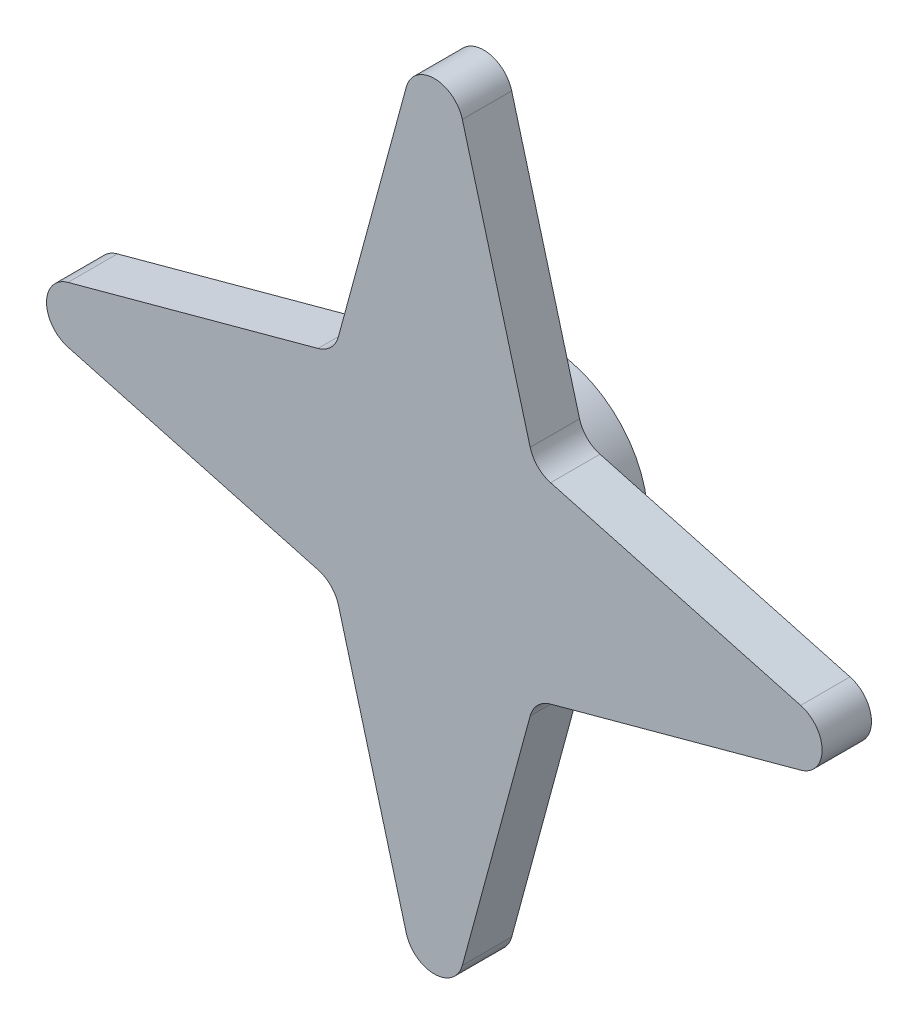
SolidWorks part; units mm, degrees
ref_plane "Front Plane" through (0, 0, 0) normal (0, 0, 1) x (1, 0, 0)
ref_plane "Top Plane" through (0, 0, 0) normal (0, 1, 0) x (1, 0, 0)
ref_plane "Right Plane" through (0, 0, 0) normal (1, 0, 0) x (0, 0, -1)
sketch "Sketch1" plane through (0, 0, 0) normal (0, 0, 1) x (1, 0, 0)
  line L0 (-1.7, 0) -> (-18.5, 0) construction
  line L1 (-8.6, 3.45) -> (-7.5895, 2.4395)
  line L2 (-8.6, -3.45) -> (-7.5895, -2.4395)
  line L5 (-8.6, 3.45) -> (-17.7618, 0.9651)
  line L6 (-8.6, -3.45) -> (-17.7618, -0.9651)
  line L8 (-8.6, -3.45) -> (-1.7, -3.45) construction
  line L9 (-8.6, -3.45) -> (-8.6, 3.45) construction
  line L10 (-8.6, 3.45) -> (-1.7, 3.45) construction
  line L11 (-1.7, -3.45) -> (-1.7, 3.45) construction
  line L12 (-8.6, -3.45) -> (-1.7, 3.45) construction
  line L13 (-8.6, 3.45) -> (-1.7, -3.45) construction
  circle A0 centre (-5.15, 0) radius 3.45
  arc A1 (-17.7618, 0.9651) -> (-17.7618, -0.9651) centre (-17.5, 0) ccw
  circle A2 centre (-5.15, 0) radius 2.5 construction
  circle A3 centre (-5.15, 0) radius 2.5
  dimension "D1" = 6.9
  dimension "D3" = 2
  dimension "D2" = 16.8
extrude "Boss-Extrude1" add sketch "Sketch1" against normal blind 2.2 contours A0 A3 region at (-3.8671, 3.0972, 0)
ref_axis "Axis1" through (-5.15, 0, -12.1812) along (0, 0, 1)
ref_plane "Plane3" through (-2.575, -2.575, 0) normal (0.7071, 0.7071, 0) x (0, 0, -1)
ref_plane "Plane4" through (-2.575, 2.575, 0) normal (0.7071, -0.7071, 0) x (0, 0, -1)
extrude "Boss-Extrude4" add sketch "Sketch1<9>" along normal blind 1.7 contours A0 A3 | A3 region at (-3.8671, 3.0972, 0) region at (-5.15, 0, 0)
sketch "Sketch1<9>" plane through (0, 0, 0) normal (0, 0, 1) x (1, 0, 0) same geometry as "Sketch1"
extrude "Boss-Extrude5" add sketch "Sketch1<10>" along normal blind 1.7 contours L5 A1 L6 L2 A0 L1 region at (-12.2251, 0, 0)
sketch "Sketch1<10>" plane through (0, 0, 0) normal (0, 0, 1) x (1, 0, 0) same geometry as "Sketch1"
mirror "Mirror2" about plane through (-2.575, 2.575, 0) normal (0.7071, -0.7071, 0) of "Boss-Extrude5"
mirror "Mirror3" about plane through (-2.575, -2.575, 0) normal (0.7071, 0.7071, 0) of "Mirror2", "Boss-Extrude5"
fillet "Fillet1" radius 1 4 edges at (-8.6, -3.45, 0.85) (-8.6, 3.45, 0.85) (-1.7, 3.45, 0.85) (-1.7, -3.45, 0.85)
